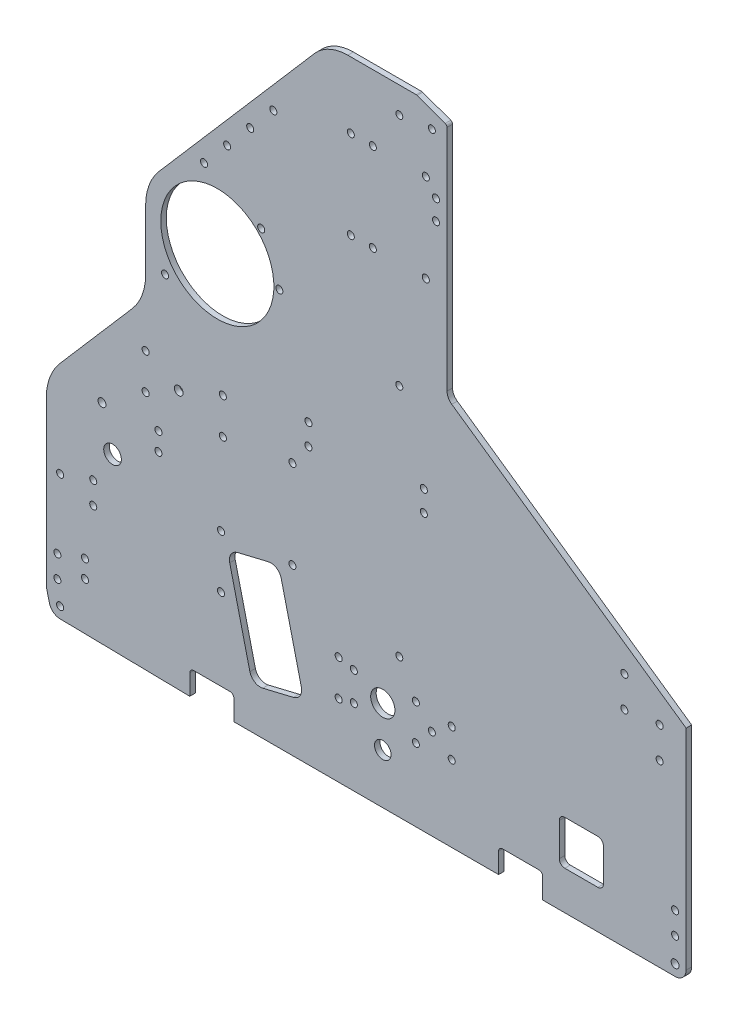
SolidWorks part; units mm, degrees
ref_plane "Front Plane" through (0, 0, 0) normal (0, 0, 1) x (1, 0, 0)
ref_plane "Top Plane" through (0, 0, 0) normal (0, 1, 0) x (1, 0, 0)
ref_plane "Right Plane" through (0, 0, 0) normal (1, 0, 0) x (0, 0, -1)
sketch "Sketch1" plane through (0, 0, 0) normal (0, 0, 1) x (1, 0, 0)
  line L0 (82.55, -20.32) -> (82.55, -6.35)
  line L2 (0, 0) -> (0, 157.48)
  line L4 (368.3, -20.32) -> (368.3, 106.68)
  line L5 (82.55, -6.35) -> (107.95, -6.35)
  line L6 (107.95, -6.35) -> (107.95, -20.32)
  line L7 (107.95, -20.32) -> (260.35, -20.32)
  line L8 (260.35, -20.32) -> (260.35, -6.35)
  line L9 (260.35, -6.35) -> (285.75, -6.35)
  line L10 (285.75, -6.35) -> (285.75, -20.32)
  line L11 (285.75, -20.32) -> (368.3, -20.32)
  line L12 (361.95, 12.7) -> (368.3, 12.7) construction
  line L13 (0, 0) -> (6.35, 0) construction
  line L14 (0.1896, -7.8901) -> (1.7771, -14.2401)
  line L15 (7.8295, -19.0491) -> (82.55, -20.32)
  line L16 (0, 0) -> (0, -6.35)
  line L17 (76.2, 128.905) -> (79.375, 128.905) construction
  line L18 (57.15, 118.5863) -> (101.6, 118.5862) construction
  line L19 (57.15, 118.5863) -> (57.15, 139.2238) construction
  line L20 (101.6, 118.5862) -> (101.6, 139.2237) construction
  line L21 (57.15, 139.2238) -> (101.6, 139.2237) construction
  line L22 (57.15, 118.5863) -> (101.6, 139.2237) construction
  line L23 (101.6, 118.5862) -> (57.15, 139.2238) construction
  line L25 (203.2, 59.805) -> (203.2, 194.805) construction
  line L26 (203.2, 194.805) -> (203.2, 329.805) construction
  line L27 (355.6, 332.105) -> (330.2, 332.105) construction
  line L28 (330.2, 332.105) -> (330.2, 217.805) construction
  line L29 (330.2, 217.805) -> (355.6, 217.805) construction
  line L30 (355.6, 217.805) -> (355.6, 332.105) construction
  line L31 (203.2, 344.805) -> (203.2, 194.805) construction
  line L32 (50.8, 332.105) -> (76.2, 332.105) construction
  line L33 (76.2, 332.105) -> (76.2, 217.805) construction
  line L34 (50.8, 217.805) -> (50.8, 332.105) construction
  line L35 (76.2, 217.805) -> (50.8, 217.805) construction
  line L36 (213.2, 344.805) -> (230.6638, 338.455)
  line L37 (203.2, 344.805) -> (161.925, 344.805)
  line L38 (203.2, 344.805) -> (213.2, 344.805)
  line L39 (348.5362, 344.805) -> (413.4623, 344.805)
  line L40 (348.5362, 344.805) -> (230.6638, 344.805) construction
  line L42 (161.925, 344.805) -> (0, 157.48)
  line L44 (230.6638, 338.455) -> (230.6638, 202.565)
  line L45 (230.6638, 202.565) -> (368.3, 106.68)
  line L46 (213.2, 344.805) -> (-141.0713, 344.805) construction
  circle A0 centre (6.35, 0) radius 2.032
  circle A1 centre (6.35, 12.7) radius 2.032
  circle A2 centre (361.95, 0) radius 2.032
  circle A3 centre (361.95, 12.7) radius 2.032
  arc A5 (1.7771, -14.2401) -> (7.8295, -19.0491) centre (7.9375, -12.7) ccw
  circle A6 centre (7.9375, -12.7) radius 2.032
  arc A7 (0, -6.35) -> (0.1896, -7.8901) centre (6.35, -6.35) ccw
  circle A8 centre (38.1, 78.105) radius 5.08
  circle A9 centre (76.2, 128.905) radius 2.54
  circle A10 centre (101.6, 118.5862) radius 2.032
  circle A11 centre (101.6, 139.2237) radius 2.032
  circle A12 centre (57.15, 139.2238) radius 2.032
  circle A13 centre (57.15, 118.5863) radius 2.032
  circle A15 centre (203.2, 59.805) radius 2
  circle A16 centre (203.2, 194.805) radius 2
  circle A17 centre (203.2, 329.805) radius 2
  circle A18 centre (63.5, 313.055) radius 2.032
  circle A20 centre (355.6, 332.105) radius 2.032
  circle A21 centre (330.2, 332.105) radius 2.032
  circle A22 centre (355.6, 217.805) radius 2.032
  circle A23 centre (330.2, 217.805) radius 2.032
  circle A24 centre (50.8, 332.105) radius 2.032
  circle A25 centre (76.2, 332.105) radius 2.032
  circle A26 centre (50.8, 217.805) radius 2.032
  circle A27 centre (76.2, 217.805) radius 2.032
  circle A28 centre (221.9319, 332.105) radius 2
  circle A29 centre (224.3138, 298.831) radius 2.032
  circle A30 centre (353.06, 100.7351) radius 2.032
  circle A31 centre (332.74, 115.9751) radius 2.032
  circle A32 centre (332.74, 98.1951) radius 2.032
  circle A33 centre (353.06, 82.9551) radius 2.032
  circle A34 centre (117.3562, 280.4276) radius 2.032
  circle A35 centre (104.0678, 265.0548) radius 2.032
  circle A36 centre (90.7795, 249.682) radius 2.032
  circle A38 centre (130.6445, 295.8004) radius 2.032
  circle A39 centre (68.326, 182.9237) radius 2.032
  circle A40 centre (224.3138, 287.401) radius 2.032
  point P82 (203.2, 344.805)
  point P83 (221.9319, 341.63)
  point P90 (368.3, 62.484)
  dimension "D6" = 4.064
  dimension "D10" = 6.35
  dimension "D11" = 4.064
  dimension "D17" = 38.1
  dimension "D27" = 4
  dimension "D31" = 4.064
  dimension "D32" = 41.275
  dimension "D36" = 4.064
  dimension "D47" = 39.624
  dimension "D48" = 4.064
  dimension "D25" = 5.08
  dimension "D26" = 4.064
  dimension "D52" = 4.064
  dimension "D65" = 4.064
  dimension "D69" = 10.16
  dimension "D2" = 127
  dimension "D3" = 13.97
  dimension "D4" = 25.4
  dimension "D5" = 152.4
  dimension "D7" = 12.7
  dimension "D8" = 6.35
  dimension "D9" = 20.32
  dimension "D12" = 12.7
  dimension "D13" = 1.5875
  dimension "D14" = 82.55
  dimension "D15" = 368.3
  dimension "D16" = 6.35
  dimension "D18" = 98.425
  dimension "D19" = 38.1
  dimension "D20" = 50.8
  dimension "D21" = 3.175
  dimension "D22" = 270
  dimension "D23" = 20.6375
  dimension "D24" = 44.45
  dimension "D28" = 135
  dimension "D29" = 12.7
  dimension "D30" = 15
  dimension "D33" = 63.5
  dimension "D34" = 27.4638
  dimension "D35" = 12.7
  dimension "D37" = 114.3
  dimension "D38" = 25.4
  dimension "D39" = 12.7
  dimension "D40" = 157.48
  dimension "D41" = 142.24
  dimension "D42" = 365.125
  dimension "D43" = 10
  dimension "D44" = 6.35
  dimension "D45" = 31.75
  dimension "D46" = 6.35
  dimension "D49" = 6.35
  dimension "D50" = 203.2
  dimension "D51" = 15.24
  dimension "D53" = 17.78
  dimension "D54" = 17.78
  dimension "D55" = 20.32
  dimension "D56" = 15.24
  dimension "D57" = 92.202
  dimension "D58" = 8.382
  dimension "D59" = 20.32
  dimension "D60" = 20.32
  dimension "D61" = 8.382
  dimension "D62" = 20.32
  dimension "D63" = 8.382
  dimension "D64" = 8.382
  dimension "D66" = 35.052
  dimension "D67" = 68.326
  dimension "D68" = 11.43
extrude "Boss-Extrude1" add sketch "Sketch1" along normal blind 3.175 contours L16 A7 L14 A5 L15 L2 A0 A1 A6 region at (171.4477, 119.565, 0)
fillet "Fillet1" radius 2.286 4 edges at (285.75, -6.35, 1.5875) (107.95, -6.35, 1.5875) (260.35, -6.35, 1.5875) (82.55, -6.35, 1.5875)
fillet "Fillet2" radius 6.35 1 edges at (230.6638, 202.565, 1.5875)
sketch "Sketch2" plane through (0, 0, 0) normal (0, 0, -1) x (-1, 0, 0)
  circle A0 centre (-100.5528, 71.086) radius 2.032 construction
  circle A1 centre (-100.5528, 40.606) radius 2.032 construction
  circle A2 centre (-22.225, 18.2025) radius 2.032 construction
  circle A3 centre (-22.225, 8.0425) radius 2.032 construction
  circle A4 centre (-100.5528, 71.086) radius 2.032
  circle A5 centre (-100.5528, 40.606) radius 2.032
  circle A6 centre (-22.225, 18.2025) radius 2.032
  circle A7 centre (-22.225, 8.0425) radius 2.032
extrude "Cut-Extrude1" cut sketch "Sketch2" against normal through all
fillet "Fillet3" radius 1.5875 2 edges at (230.6638, 338.455, 1.5875) (213.2, 344.805, 1.5875)
sketch "Sketch3" plane through (0, 0, 3.175) normal (0, 0, 1) x (1, 0, 0)
  line L0 (132.9524, 63.2646) -> (132.7215, 64.2281) construction
  line L1 (128.3814, 66.8897) -> (110.6828, 62.6472) construction
  line L2 (114.5132, 58.4237) -> (126.8822, 61.3887) construction
  line L3 (108.0212, 58.3071) -> (108.2522, 57.3436) construction
  line L4 (131.2006, 57.703) -> (140.0164, 20.9265) construction
  line L5 (144.0993, 16.7636) -> (132.9524, 63.2646) construction
  line L6 (108.2522, 57.3436) -> (119.3991, 10.8426) construction
  line L7 (121.1509, 16.4042) -> (112.3351, 53.1807) construction
  line L8 (119.3991, 10.8426) -> (119.6301, 9.8791) construction
  line L9 (144.3303, 15.8001) -> (144.0993, 16.7636) construction
  line L10 (137.8383, 15.6835) -> (125.4694, 12.7185) construction
  line L11 (123.9701, 7.2175) -> (141.6687, 11.4601) construction
  line L12 (132.9524, 63.2646) -> (132.7215, 64.2281)
  line L13 (128.3814, 66.8897) -> (110.6828, 62.6472)
  line L14 (114.5132, 58.4237) -> (126.8822, 61.3887)
  line L15 (108.0212, 58.3071) -> (108.2522, 57.3436)
  line L16 (131.2006, 57.703) -> (140.0164, 20.9265)
  line L17 (144.0993, 16.7636) -> (132.9524, 63.2646)
  line L18 (108.2522, 57.3436) -> (119.3991, 10.8426)
  line L19 (121.1509, 16.4042) -> (112.3351, 53.1807)
  line L20 (119.3991, 10.8426) -> (119.6301, 9.8791)
  line L21 (144.3303, 15.8001) -> (144.0993, 16.7636)
  line L22 (137.8383, 15.6835) -> (125.4694, 12.7185)
  line L23 (123.9701, 7.2175) -> (141.6687, 11.4601)
  line L24 (127.7894, 69.3598) -> (110.0908, 65.1172)
  line L25 (105.5512, 57.715) -> (105.7822, 56.7515)
  line L26 (105.7822, 56.7515) -> (116.9291, 10.2505)
  line L27 (116.9291, 10.2505) -> (117.16, 9.287)
  line L28 (124.5622, 4.7475) -> (142.2608, 8.99)
  line L29 (146.8003, 16.3922) -> (146.5694, 17.3557)
  line L30 (146.5694, 17.3557) -> (135.4225, 63.8567)
  line L31 (135.4225, 63.8567) -> (135.1915, 64.8202)
  line L32 (14.605, -0.1369) -> (103.7278, 32.3011) construction
  line L33 (14.605, -0.1369) -> (103.7278, 32.3011)
  line L34 (0, -6.35) -> (0, 157.48) construction
  line L35 (-39.6666, 74.7152) -> (103.7278, 126.9065) construction
  line L36 (26.9875, 46.9531) -> (26.9875, 59.6531) construction
  line L37 (107.95, -20.32) -> (260.35, -20.32) construction
  line L38 (64.5259, 92.5258) -> (64.5259, 102.9405) construction
  arc A0 (132.7215, 64.2281) -> (128.6308, 66.9403) centre (129.2206, 63.3889) ccw construction
  arc A1 (110.6828, 62.6472) -> (110.4377, 62.5791) centre (111.522, 59.1463) ccw construction
  arc A2 (128.6308, 66.9403) -> (128.3814, 66.8897) centre (129.2206, 63.3889) ccw construction
  arc A3 (110.4377, 62.5791) -> (108.0212, 58.3071) centre (111.522, 59.1463) ccw construction
  arc A4 (119.6301, 9.8791) -> (123.7207, 7.1669) centre (123.1309, 10.7183) ccw construction
  arc A5 (141.9139, 11.5281) -> (144.3303, 15.8001) centre (140.8295, 14.9609) ccw construction
  arc A6 (141.6687, 11.4601) -> (141.9139, 11.5281) centre (140.8295, 14.9609) ccw construction
  arc A7 (123.7207, 7.1669) -> (123.9701, 7.2175) centre (123.1309, 10.7183) ccw construction
  arc A8 (132.7215, 64.2281) -> (128.6308, 66.9403) centre (129.2206, 63.3889) ccw
  arc A9 (110.6828, 62.6472) -> (110.4377, 62.5791) centre (111.522, 59.1463) ccw
  arc A10 (128.6308, 66.9403) -> (128.3814, 66.8897) centre (129.2206, 63.3889) ccw
  arc A11 (110.4377, 62.5791) -> (108.0212, 58.3071) centre (111.522, 59.1463) ccw
  arc A12 (119.6301, 9.8791) -> (123.7207, 7.1669) centre (123.1309, 10.7183) ccw
  arc A13 (141.9139, 11.5281) -> (144.3303, 15.8001) centre (140.8295, 14.9609) ccw
  arc A14 (141.6687, 11.4601) -> (141.9139, 11.5281) centre (140.8295, 14.9609) ccw
  arc A15 (123.7207, 7.1669) -> (123.9701, 7.2175) centre (123.1309, 10.7183) ccw
  arc A16 (110.0908, 65.1172) -> (109.6726, 65.0012) centre (111.522, 59.1463) ccw
  arc A17 (109.6726, 65.0012) -> (105.5512, 57.715) centre (111.522, 59.1463) ccw
  arc A18 (117.16, 9.287) -> (124.1369, 4.6613) centre (123.1309, 10.7183) ccw
  arc A19 (124.1369, 4.6613) -> (124.5622, 4.7475) centre (123.1309, 10.7183) ccw
  arc A20 (142.2608, 8.99) -> (142.6789, 9.1061) centre (140.8295, 14.9609) ccw
  arc A21 (142.6789, 9.1061) -> (146.8003, 16.3922) centre (140.8295, 14.9609) ccw
  arc A22 (135.1915, 64.8202) -> (128.2147, 69.446) centre (129.2206, 63.3889) ccw
  arc A23 (128.2147, 69.446) -> (127.7894, 69.3598) centre (129.2206, 63.3889) ccw
  circle A26 centre (134.1438, 208.2281) radius 2.032 construction
  circle A33 centre (26.9875, 46.9531) radius 2.032
  circle A34 centre (26.9875, 59.6531) radius 2.032
  circle A35 centre (7.9375, 53.3031) radius 2.032
  circle A37 centre (32.0306, 100.8109) radius 31.75 construction
  circle A38 centre (32.0306, 100.8109) radius 2.286
  circle A39 centre (123.682, 233.4851) radius 2.032 construction
  circle A40 centre (64.5259, 102.9405) radius 2.032
  circle A41 centre (64.5259, 92.5258) radius 2.032
  circle A42 centre (134.1438, 208.2281) radius 2.032
  circle A43 centre (123.682, 233.4851) radius 2.032
  ellipse E0 centre (124.5974, 48.8487) end of major axis (128.5376, 61.3578) minor radius 6 (131.2006, 57.703) -> (126.8822, 61.3887) ccw construction
  ellipse E1 centre (122.2349, 48.2824) end of major axis (113.0518, 57.6456) minor radius 6 (114.5132, 58.4237) -> (112.3351, 53.1807) ccw construction
  ellipse E2 centre (127.7541, 25.2585) end of major axis (131.6942, 37.7675) minor radius 6 (121.1509, 16.4042) -> (125.4694, 12.7185) ccw construction
  ellipse E3 centre (130.1166, 25.8248) end of major axis (139.2998, 16.4616) minor radius 6 (137.8383, 15.6835) -> (140.0164, 20.9265) ccw construction
  ellipse E4 centre (124.5974, 48.8487) end of major axis (120.6573, 36.3397) minor radius 6 (131.2006, 57.703) -> (126.8822, 61.3887) ccw
  ellipse E5 centre (122.2349, 48.2824) end of major axis (131.4181, 38.9192) minor radius 6 (114.5132, 58.4237) -> (112.3351, 53.1807) ccw
  ellipse E6 centre (127.7541, 25.2585) end of major axis (131.6942, 37.7675) minor radius 6 (121.1509, 16.4042) -> (125.4694, 12.7185) ccw
  ellipse E7 centre (130.1166, 25.8248) end of major axis (139.2998, 16.4616) minor radius 6 (137.8383, 15.6835) -> (140.0164, 20.9265) ccw
  point P93 (26.9875, 53.3031)
  point P115 (32.0306, 100.8109)
  dimension "D3" = 63.5
  dimension "D4" = 4.572
  dimension "D8" = 4.064
  dimension "D2" = 88.9
  dimension "D5" = 7.9375
  dimension "D6" = 19.05
  dimension "D7" = 73.6231
  dimension "D9" = 12.7
  dimension "D10" = 10.4147
  dimension "D11" = 37.5384
  dimension "D12" = 45.5727
  dimension "D1" = 2.54
extrude "Cut-Extrude2" cut sketch "Sketch3" against normal through all contours A22 A23 L24 A16 A17 L25 L26 L27 A18 A19 L28 A20 A21 L29 L30 L31 A15 A12 L20 L18 L15 A11 A9 L13 A10 A8 L12 L17 L21 A13 A14 L23 | A12 A15 L23 A14 A13 L21 L17 L12 A8 A10 L13 A9 A11 L15 L18 L20 E7 L22 E6 L19 E5 L14 E4 L16 | L22 E7 L16 E4 L14 E5 L19 E6 | A38 | A41 | A40 | A35 | A34 | A33 | A43 | A42 region at (137.844, 39.8506, 3.175) region at (126.1758, 37.0536, 3.175) region at (128.1544, 68.6507, 3.175) region at (32.0306, 100.8109, 3.175) region at (64.5259, 102.9405, 3.175) region at (64.5259, 92.5258, 3.175)
sketch "Sketch4" plane through (0, 0, 3.175) normal (0, 0, 1) x (1, 0, 0)
  line L0 (57.15, 139.2238) -> (101.6, 139.2237) construction
  line L1 (168.275, 21.4312) -> (212.725, 21.4312) construction
  line L2 (168.275, 21.4312) -> (168.275, 42.0687) construction
  line L3 (168.275, 42.0687) -> (212.725, 42.0687) construction
  line L4 (212.725, 21.4312) -> (212.725, 42.0687) construction
  line L5 (168.275, 21.4312) -> (212.725, 42.0687) construction
  line L6 (168.275, 42.0687) -> (212.725, 21.4312) construction
  line L7 (57.15, 118.5863) -> (57.15, 139.2238) construction
  line L8 (107.95, -20.32) -> (260.35, -20.32) construction
  line L9 (193.675, 31.75) -> (177.005, 31.75) construction
  line L10 (190.5, 31.75) -> (193.675, 31.75) construction
  line L11 (6.35, 12.7) -> (361.95, 12.7) construction
  line L12 (107.95, -6.35) -> (107.95, -20.32) construction
  line L13 (193.675, 31.75) -> (220.6625, 31.75) construction
  line L14 (177.005, 23.4569) -> (177.005, 40.0431) construction
  line L15 (213.2, 44.805) -> (193.2, 44.805) construction
  line L16 (213.2, 44.805) -> (213.2, 344.805) construction
  line L17 (213.2, 344.805) -> (193.2, 344.805) construction
  line L18 (193.2, 44.805) -> (193.2, 344.805) construction
  line L19 (213.2, 44.805) -> (193.2, 344.805) construction
  line L20 (213.2, 344.805) -> (193.2, 44.805) construction
  line L21 (226.9319, 332.105) -> (226.9319, 31.75) construction
  line L22 (237.33, 40.0431) -> (233.3612, 40.0431) construction
  line L23 (237.33, 23.4569) -> (233.3612, 23.4569) construction
  circle A0 centre (168.275, 42.0687) radius 2.032
  circle A1 centre (212.725, 42.0687) radius 2.032
  circle A2 centre (212.725, 21.4312) radius 2.032
  circle A3 centre (168.275, 21.4312) radius 2.032
  circle A4 centre (193.675, 31.75) radius 6.985
  circle A7 centre (220.6625, 31.75) radius 14.2875 construction
  circle A8 centre (193.675, 31.75) radius 12.7 construction
  circle A9 centre (177.005, 40.0431) radius 2.032
  circle A10 centre (177.005, 23.4569) radius 2.032
  circle A11 centre (237.33, 40.0431) radius 2.032 construction
  circle A12 centre (237.33, 23.4569) radius 2.032 construction
  circle A13 centre (193.675, 8.4667) radius 4.7625
  circle A14 centre (221.9319, 31.75) radius 2.032
  circle A15 centre (221.9319, 31.75) radius 5 construction
  circle A16 centre (221.9319, 332.105) radius 5 construction
  circle A17 centre (233.3612, 23.4569) radius 2.032
  circle A18 centre (233.3612, 40.0431) radius 2.032
  point P0 (190.5, 31.75)
  point P26 (203.2, 194.805)
  point P38 (177.005, 31.75)
  dimension "D1" = 4.064
  dimension "D4" = 13.97
  dimension "D7" = 9.525
  dimension "D10" = 25.4
  dimension "D11" = 28.575
  dimension "D16" = 10
  dimension "D17" = 4.064
  dimension "D18" = 10
  dimension "D2" = 52.07
  dimension "D3" = 3.175
  dimension "D5" = 82.55
  dimension "D6" = 26.9875
  dimension "D8" = 20
  dimension "D9" = 300
  dimension "D12" = 16.67
  dimension "D13" = 16.5862
  dimension "D14" = 60.325
  dimension "D15" = 23.2833
  dimension "D19" = 3.9688
extrude "Cut-Extrude3" cut sketch "Sketch4" against normal through all
sketch "Sketch5" plane through (0, 0, 0) normal (0, 0, -1) x (-1, 0, 0)
  line L0 (-57.15, 223.5947) -> (-57.15, 165.3337)
  line L1 (-161.925, 344.805) -> (-52.7201, 218.4699) construction
  line L2 (-57.15, 165.3337) -> (0, 99.219)
  line L3 (0, -6.35) -> (0, 157.48) construction
  line L5 (-50.4199, 215.8089) -> (0, 157.48) construction
  line L6 (-57.15, 223.5947) -> (0, 157.48)
  line L7 (0, 157.48) -> (0, 99.219)
  line L8 (-361.95, -13.97) -> (-368.3, -13.97) construction
  line L9 (-361.95, -13.97) -> (-361.95, -20.32) construction
  line L10 (-285.75, -20.32) -> (-368.3, -20.32) construction
  line L11 (-368.3, -20.32) -> (-368.3, 106.68) construction
  circle A0 centre (-98.425, 208.2281) radius 32.5437
  circle A2 centre (-361.95, -13.97) radius 2.286
  dimension "D3" = 65.0875
  dimension "D7" = 4.572
  dimension "D1" = 38.1
  dimension "D2" = 57.15
  dimension "D4" = 41.275
  dimension "D5" = 41.275
  dimension "D6" = 6.35
extrude "Cut-Extrude5" cut sketch "Sketch5" against normal through all contours A0 | L7 L6 L0 L2 | A2 region at (28.575, 161.4068, 0) region at (98.425, 208.2281, 0)
fillet "Fillet4" radius 31.75 3 edges at (0, 99.219, 1.5875) (57.15, 165.3337, 1.5875) (57.15, 223.5947, 1.5875)
sketch "Sketch6" plane through (0, 0, 3.175) normal (0, 0, 1) x (1, 0, 0)
  line L0 (285.75, -20.32) -> (368.3, -20.32) construction
  line L1 (298.45, 27.305) -> (317.5, 27.305)
  line L2 (295.275, 24.13) -> (295.275, 5.08)
  line L3 (298.45, 1.905) -> (317.5, 1.905)
  line L4 (320.675, 24.13) -> (320.675, 5.08)
  line L5 (295.275, 27.305) -> (320.675, 1.905) construction
  line L6 (295.275, 1.905) -> (320.675, 27.305) construction
  line L7 (368.3, -20.32) -> (368.3, 106.68) construction
  arc A0 (295.275, 5.08) -> (298.45, 1.905) centre (298.45, 5.08) ccw
  arc A1 (317.5, 1.905) -> (320.675, 5.08) centre (317.5, 5.08) ccw
  arc A2 (317.5, 27.305) -> (320.675, 24.13) centre (317.5, 24.13) cw
  arc A3 (298.45, 27.305) -> (295.275, 24.13) centre (298.45, 24.13) ccw
  point P0 (307.975, 14.605)
  dimension "D2" = 3.175
  dimension "D1" = 25.4
  dimension "D3" = 22.225
  dimension "D4" = 47.625
extrude "Cut-Extrude6" cut sketch "Sketch6" against normal through all
fillet "Fillet5" radius 25.4 1 edges at (161.925, 344.805, 1.5875)
sketch "Sketch8" plane through (0, 0, 0) normal (0, 0, -1) x (-1, 0, 0)
  circle A0 centre (-187.96, 306.705) radius 2.032 construction
  arc A1 (-176.3652, 304.9998) -> (-176.3652, 308.4102) centre (-175.26, 306.705) ccw construction
  arc A2 (-219.0586, 304.7695) -> (-219.0586, 308.6405) centre (-218.44, 306.705) ccw construction
  circle A3 centre (-205.74, 306.705) radius 2.032 construction
  arc A4 (-219.0586, 253.9695) -> (-219.0586, 257.8405) centre (-218.44, 255.905) ccw construction
  circle A5 centre (-205.74, 255.905) radius 2.032 construction
  circle A6 centre (-187.96, 255.905) radius 2.032 construction
  arc A7 (-176.3652, 254.1998) -> (-176.3652, 257.6102) centre (-175.26, 255.905) ccw construction
  circle A8 centre (-187.96, 306.705) radius 2.032
  arc A9 (-176.3652, 304.9998) -> (-176.3652, 308.4102) centre (-175.26, 306.705) ccw
  arc A10 (-219.0586, 304.7695) -> (-219.0586, 308.6405) centre (-218.44, 306.705) ccw
  circle A11 centre (-205.74, 306.705) radius 2.032
  arc A12 (-219.0586, 253.9695) -> (-219.0586, 257.8405) centre (-218.44, 255.905) ccw
  circle A13 centre (-205.74, 255.905) radius 2.032
  circle A14 centre (-187.96, 255.905) radius 2.032
  arc A15 (-176.3652, 254.1998) -> (-176.3652, 257.6102) centre (-175.26, 255.905) ccw
  circle A16 centre (-218.44, 306.705) radius 2.032
  circle A17 centre (-175.26, 306.705) radius 2.032
  circle A18 centre (-175.26, 255.905) radius 2.032
  circle A19 centre (-218.44, 255.905) radius 2.032
  circle A20 centre (-218.44, 306.705) radius 3.9688
  circle A21 centre (-205.74, 306.705) radius 3.9688
  circle A22 centre (-175.26, 306.705) radius 3.9687
  circle A23 centre (-218.44, 255.905) radius 3.9688
  circle A24 centre (-205.74, 255.905) radius 3.9688
  circle A25 centre (-187.96, 255.905) radius 3.9687
  circle A26 centre (-175.26, 255.905) radius 3.9687
  circle A27 centre (-187.96, 306.705) radius 3.9687
  dimension "D1" = 7.9375
extrude "Cut-Extrude7" cut sketch "Sketch8" against normal through all contours A10 A16 | A9 A17 | A15 A18 | A12 A19 | A8 | A14 region at (175.26, 306.705, 0) region at (218.44, 306.705, 0) region at (218.44, 255.905, 0) region at (175.26, 255.905, 0)
sketch "Sketch10" plane through (0, 0, 3.175) normal (0, 0, 1) x (1, 0, 0)
  circle A4 centre (141.6425, 74.6844) radius 2.032 construction
  circle A5 centre (141.6425, 125.4844) radius 2.032 construction
  circle A6 centre (141.6425, 74.6844) radius 2.032
  circle A7 centre (141.6425, 125.4844) radius 2.032
extrude "Cut-Extrude8" cut sketch "Sketch10" against normal through all
fillet "Fillet6" radius 6.35 1 edges at (368.3, -20.32, 1.5875)
sketch "Sketch11" plane through (0, 0, 3.175) normal (0, 0, 1) x (1, 0, 0)
  ellipse E4 centre (150.8814, 138.43) end of major axis (150.8814, 140.462) minor radius 2.032
  ellipse E5 centre (150.8814, 150.495) end of major axis (150.8814, 152.527) minor radius 2.032
  ellipse E6 centre (217.3024, 150.495) end of major axis (217.3024, 152.527) minor radius 2.032
  ellipse E7 centre (217.3024, 138.43) end of major axis (217.3024, 140.462) minor radius 2.032
extrude "Cut-Extrude9" cut sketch "Sketch11" against normal through all
